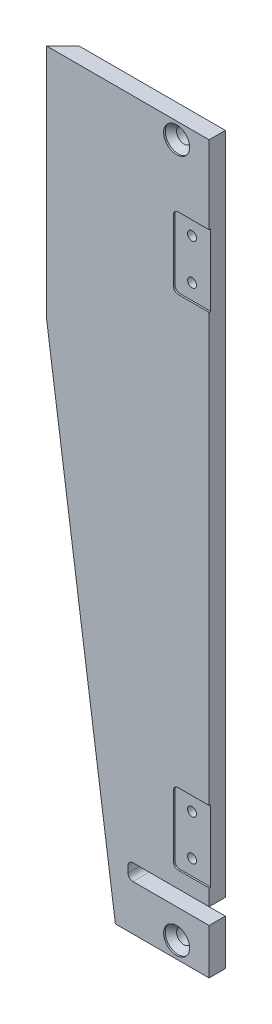
SolidWorks part; units mm, degrees
material "Oak"
ref_plane "Front Plane" through (0, 0, 0) normal (0, 0, 1) x (1, 0, 0)
ref_plane "Top Plane" through (0, 0, 0) normal (0, 1, 0) x (1, 0, 0)
ref_plane "Right Plane" through (0, 0, 0) normal (1, 0, 0) x (0, 0, -1)
sketch "Sketch1" plane through (0, 0, 0) normal (0, 0, 1) x (1, 0, 0)
  line L0 (0, 0) -> (-100, 0)
  line L1 (-100, 0) -> (-100, -146)
  line L2 (-100, -146) -> (-57.6972, -447)
  line L3 (-57.6972, -447) -> (0, -447)
  line L4 (0, -447) -> (0, 0)
  dimension "D1" = 100
  dimension "D2" = 447
  dimension "D3" = 8
  dimension "D4" = 146
extrude "Boss-Extrude1" add sketch "Sketch1" along normal blind 10
chamfer "Chamfer1" distance 10 angle 45 2 edges at (-78.8486, -296.5, 0) (-100, -73, 0)
hole_wizard "CSK for M8 Hex Socket Countersunk Head Screw1" positions "Sketch2" profile "Sketch3" countersink size "M8" standard "DIN" end condition through all
sketch "Sketch2" plane through (0, 0, 10) normal (0, 0, 1) x (1, 0, 0)
  point P0 (-20, -10)
  point P5 (-20, -437)
sketch "Sketch3" plane through (-20, -10, 10) normal (1, 0, 0) x (0, -1, 0)
  line L0 (0, 0) -> (0, 10)
  line L1 (0, 10) -> (4.5, 10)
  line L2 (4.5, 10) -> (4.5, 4.5)
  line L3 (4.5, 4.5) -> (8, 1)
  line L4 (8, 1) -> (8, 0)
  line L6 (8, 0) -> (0, 0)
  line L7 (-4.5, 4.5) -> (-8, 1) construction
  line L11 (0, -6.35) -> (0, 107.95) construction
  dimension "Thru Hole Dia." = 9
  dimension "Thru Hole Depth" = 10
  dimension "C'Sink Dia." = 16
  dimension "C'Sink Angle" = 90
  dimension "Head Clearance" = 1
sketch "Sketch4" plane through (0, 0, 10) normal (0, 0, 1) x (1, 0, 0)
  line L0 (0, -447) -> (0, 0) construction
  line L1 (0, -409) -> (-46.8972, -409)
  line L2 (0, -409) -> (0, -419)
  line L3 (0, -419) -> (-46.8972, -419)
  line L4 (-49.8972, -412) -> (-49.8972, -416)
  line L5 (128.1028, -368.7) -> (128.1028, -422) construction
  line L6 (332.0153, -427) -> (-50.4097, -427) construction
  arc A0 (-46.8972, -409) -> (-49.8972, -412) centre (-46.8972, -412) ccw
  arc A1 (-46.8972, -419) -> (-49.8972, -416) centre (-46.8972, -416) cw
  dimension "D4" = 3
  dimension "D1" = 178
  dimension "D2" = 10
  dimension "D3" = 8
extrude "Cut-Extrude1" cut sketch "Sketch4" against normal blind 30
sketch "Sketch5" plane through (0, 0, 10) normal (0, 0, 1) x (1, 0, 0)
  line L0 (0, -409) -> (0, 0) construction
  line L1 (-19, -48) -> (0, -48)
  line L2 (-22, -51) -> (-22, -89)
  line L3 (-19, -92) -> (0, -92)
  line L4 (0, -48) -> (0, -92)
  line L5 (-3, -50) -> (-20, -50) construction
  line L6 (-20, -90) -> (-20, -50) construction
  line L7 (-3, -90) -> (-20, -90) construction
  line L8 (-3, -357) -> (-20, -357) construction
  line L9 (-19, -355) -> (0, -355)
  line L10 (-22, -358) -> (-22, -396)
  line L11 (-19, -399) -> (0, -399)
  line L12 (0, -355) -> (0, -399)
  line L13 (-20, -397) -> (-20, -357) construction
  line L14 (-3, -397) -> (-20, -397) construction
  arc A0 (-19, -48) -> (-22, -51) centre (-19, -51) ccw
  arc A1 (-22, -89) -> (-19, -92) centre (-19, -89) ccw
  arc A2 (-22, -396) -> (-19, -399) centre (-19, -396) ccw
  arc A3 (-19, -355) -> (-22, -358) centre (-19, -358) ccw
  dimension "D7" = 3
  dimension "D1" = 2
  dimension "D2" = 2
  dimension "D3" = 2
  dimension "D4" = 2
  dimension "D5" = 2
  dimension "D6" = 2
extrude "Cut-Extrude2" cut sketch "Sketch5" against normal blind 1
sketch "Sketch6" plane through (0, 0, 9) normal (0, 0, 1) x (1, 0, 0)
  circle A0 centre (-11.5, -57.5) radius 2.75
  circle A1 centre (-11.5, -82.5) radius 2.75
  circle A2 centre (-11.5, -364.5) radius 2.75
  circle A3 centre (-11.5, -389.5) radius 2.75
  dimension "D1" = 5.5
extrude "Cut-Extrude3" cut sketch "Sketch6" against normal through all
